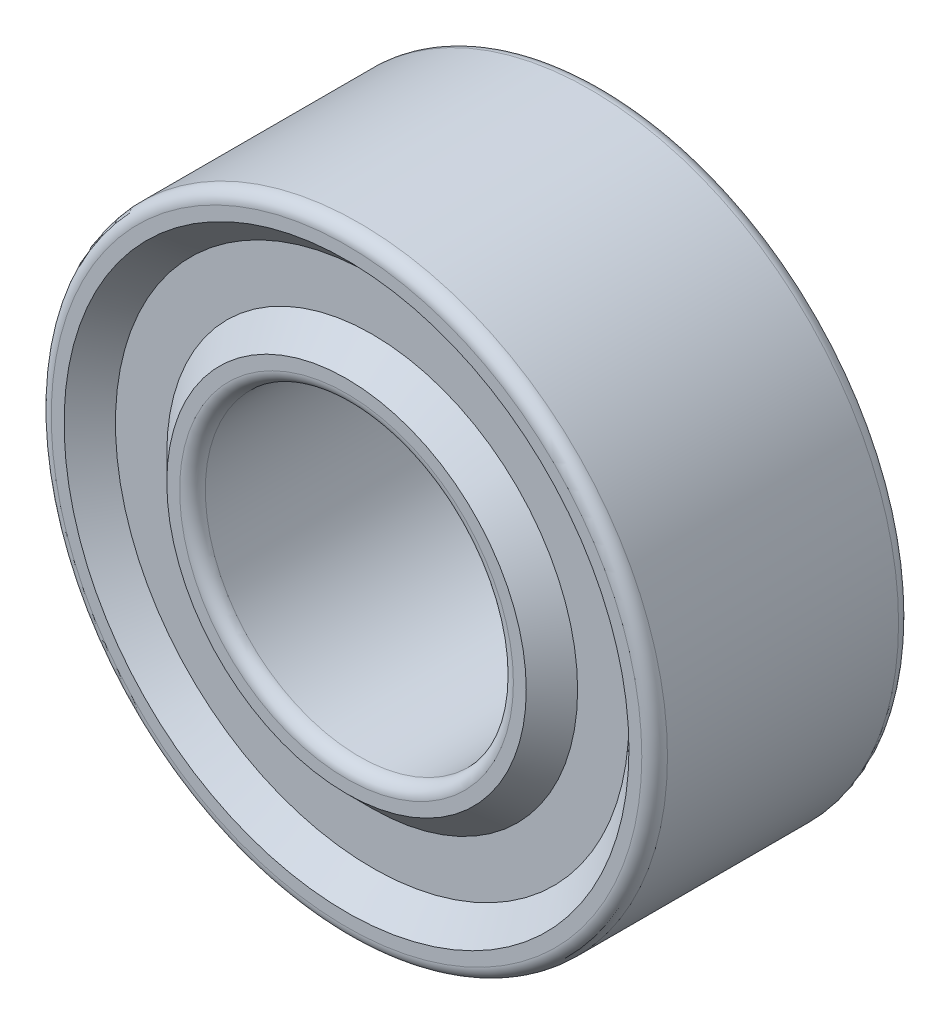
SolidWorks part; units mm, degrees
ref_plane "Front Plane" through (0, 0, 0) normal (0, 0, 1) x (1, 0, 0)
ref_plane "Top Plane" through (0, 0, 0) normal (0, 1, 0) x (1, 0, 0)
ref_plane "Right Plane" through (0, 0, 0) normal (1, 0, 0) x (0, 0, -1)
sketch "Sketch1" plane through (0, 0, 0) normal (0, 0, 1) x (1, 0, 0)
  circle A0 centre (0, 0) radius 1.5
  circle A1 centre (0, 0) radius 3
  dimension "D1" = 3
  dimension "D2" = 6
extrude "Boss-Extrude1" add sketch "Sketch1" along normal blind 2.5
sketch "Sketch2" plane through (0, 0, 2.5) normal (0, 0, 1) x (1, 0, 0)
  line L0 (0, 4.5) -> (0, 0) construction
  circle A0 centre (0, 0) radius 2.25 construction
  circle A2 centre (0, 0) radius 1.5 construction
  circle A3 centre (0, 0) radius 2.75
  circle A4 centre (0, 0) radius 1.75
  point P3 (0, 0)
  point P4 (0, 0)
  point P6 (0, 2.3287)
  point P7 (0, 0)
  point P10 (0, 2.25)
  point P13 (0, 0)
  point P15 (0, -0.0903)
  point P16 (0, 0)
  point P17 (0, 0)
  point P18 (0, 0)
  dimension "D1" = 0.5
  dimension "D2" = 0.5
  dimension "D3" = 1
  dimension "D4" = 0.25
  dimension "D5" = 2.25
extrude "Cut-Extrude1" cut sketch "Sketch2" against normal blind 0.25
extrude "Cut-Extrude2" cut sketch "Sketch2<2>" along normal blind 0.25 from offset 2.5 offset against normal yes
sketch "Sketch2<2>" plane through (0, 0, 2.5) normal (0, 0, 1) x (1, 0, 0) same geometry as "Sketch2"
fillet "Fillet1" radius 0.125 4 edges at (1.5, 0, 0) (3, 0, 0) (3, 0, 2.5) (1.5, 0, 2.5)
chamfer "Chamfer1" distance 0.25 angle 45 4 edges at (2.75, 0, 2.25) (1.75, 0, 2.25) (1.75, 0, 0.25) (2.75, 0, 0.25)
